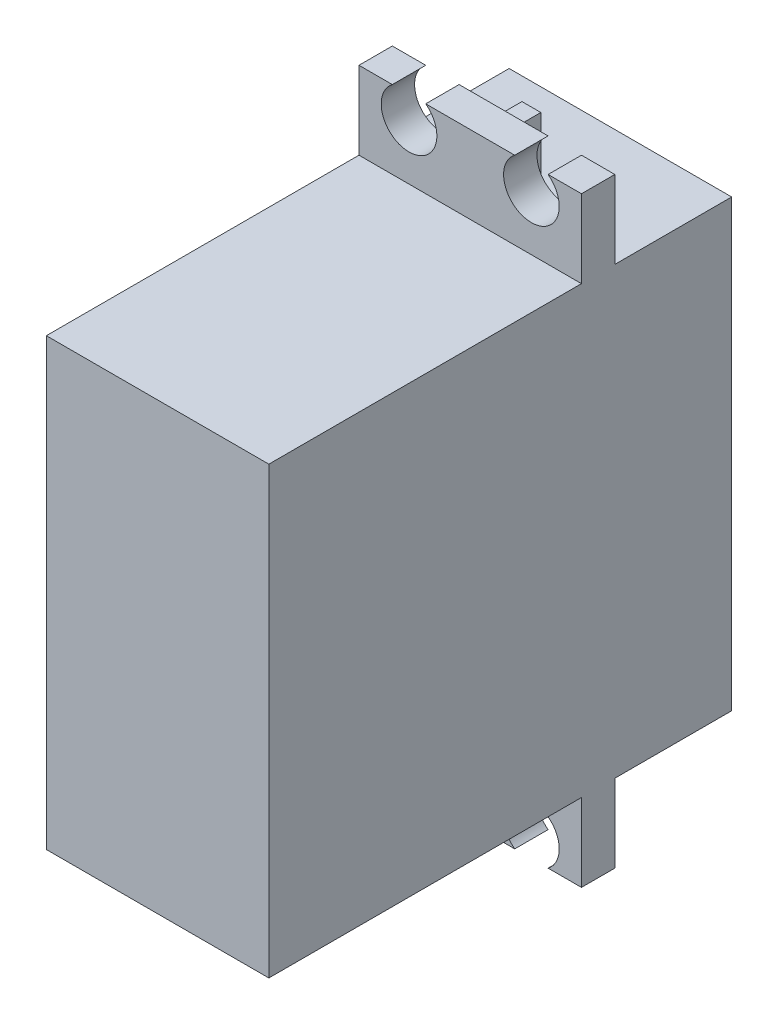
SolidWorks part; units mm, degrees
ref_plane "Front Plane" through (0, 0, 0) normal (0, 0, 1) x (1, 0, 0)
ref_plane "Top Plane" through (0, 0, 0) normal (0, 1, 0) x (1, 0, 0)
ref_plane "Right Plane" through (0, 0, 0) normal (1, 0, 0) x (0, 0, -1)
sketch "Sketch1" plane through (0, 0, 0) normal (0, 0, 1) x (1, 0, 0)
  line L1 (-10, -20) -> (10, -20)
  line L2 (-10, -20) -> (-10, 20)
  line L3 (-10, 20) -> (10, 20)
  line L4 (10, -20) -> (10, 20)
  line L5 (-10, -20) -> (10, 20) construction
  line L6 (-10, 20) -> (10, -20) construction
  point P0 (0, 0)
  dimension "D1" = 20
  dimension "D2" = 40
extrude "Boss-Extrude1" add sketch "Sketch1" along normal blind 41.6
sketch "Sketch2" plane through (0, 0, 0) normal (0, 0, -1) x (-1, 0, 0)
  line L0 (-10, 20) -> (10, 20) construction
  circle A0 centre (0, 10) radius 3
  circle A1 centre (0, 10) radius 1.5
  point P4 (0, 20)
  dimension "D1" = 6
  dimension "D3" = 3
  dimension "D2" = 10
extrude "Boss-Extrude2" add sketch "Sketch2" along normal blind 4
sketch "Sketch3" plane through (0, 0, 0) normal (0, 0, -1) x (-1, 0, 0)
  line L0 (-10, -20) -> (-10, 20) construction
  line L1 (-10, 0) -> (10, 0)
  line L2 (-10, -27) -> (-10, 27)
  line L3 (-10, 27) -> (10, 27)
  line L4 (10, -27) -> (10, 27)
  line L5 (10, 20) -> (10, -20) construction
  line L6 (-10, 20) -> (10, 20) construction
  line L7 (-10, -27) -> (10, -27)
  circle A0 centre (-5.5, 25) radius 2.5
  circle A1 centre (5.5, 25) radius 2.5
  circle A2 centre (5.5, -25) radius 2.5
  circle A3 centre (-5.5, -25) radius 2.5
  point P15 (-10, 0)
  line M6 (-10, -20) -> (10, -20)
  line M8 (10, 20) -> (-10, 20)
  dimension "D3" = 5
  dimension "D1" = 7
  dimension "D2" = 5
  dimension "D4" = 4.5
  dimension "D5" = 4.5
extrude "Boss-Extrude3" add sketch "Sketch3" along normal blind 3 from offset 13.5 contours A1 L3 A0 L2 L4 M8 | L7 A3 A2 L4 L2 M6 region at (0, -23.0005, 0) region at (0, 23.0005, 0) offset against normal yes
sketch "Sketch5" plane through (0, 0, 10.5) normal (0, 0, -1) x (-1, 0, 0)
  line L0 (10, 20) -> (-10, 20) construction
  line L1 (-0.85, 26) -> (0.85, 26)
  line L2 (-0.85, 26) -> (-0.85, 20)
  line L3 (-0.85, 20) -> (0.85, 20)
  line L4 (0.85, 26) -> (0.85, 20)
  line L5 (0.85, -20) -> (-0.85, -20)
  line L6 (0.85, -20) -> (0.85, -26)
  line L7 (0.85, -26) -> (-0.85, -26)
  line L8 (-0.85, -20) -> (-0.85, -26)
  line L9 (-10, -20) -> (10, -20) construction
  point P6 (0, 20)
  point P7 (0, 20)
  point P13 (0, -20)
  point P16 (0, -20)
  dimension "D1" = 6
  dimension "D2" = 1.7
  dimension "D3" = 6
  dimension "D4" = 1.7
extrude "Boss-Extrude4" add sketch "Sketch5" along normal blind 2.5
